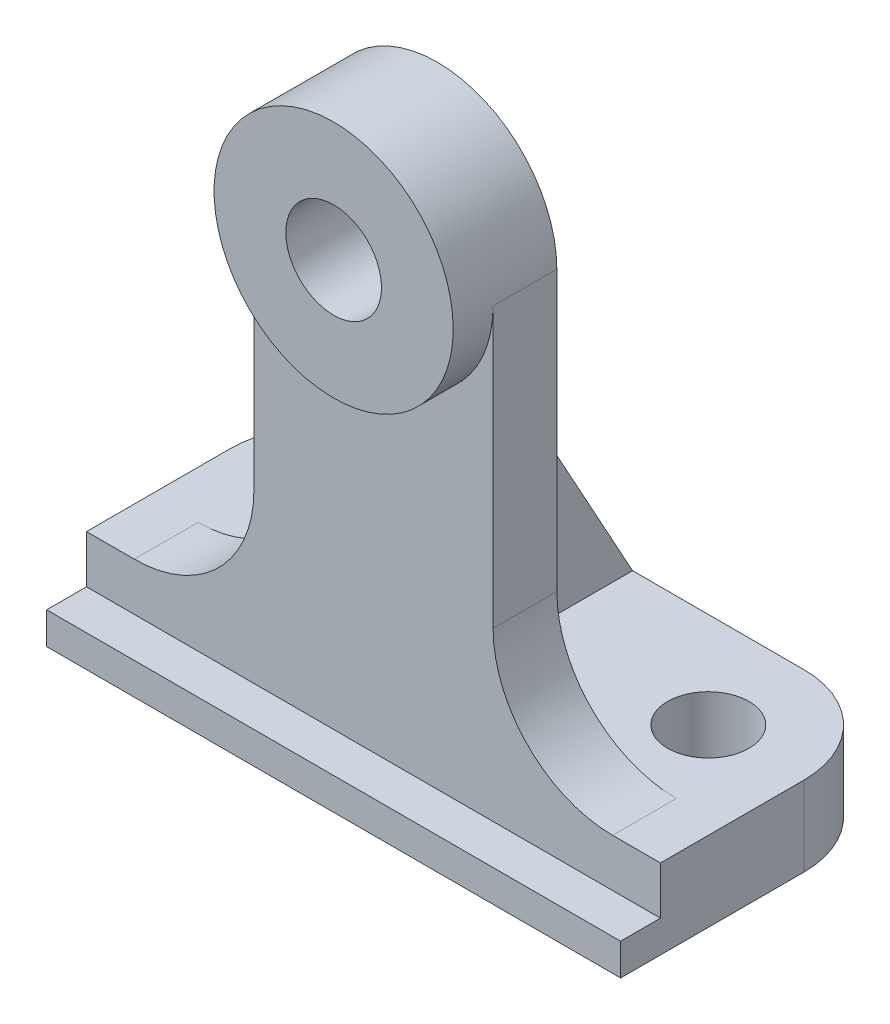
SolidWorks part; units mm, degrees
ref_plane "Front Plane" through (0, 0, 0) normal (0, 0, 1) x (1, 0, 0)
ref_plane "Top Plane" through (0, 0, 0) normal (0, 1, 0) x (1, 0, 0)
ref_plane "Right Plane" through (0, 0, 0) normal (1, 0, 0) x (0, 0, -1)
sketch "Sketch1" plane through (0, 0, 0) normal (0, 0, 1) x (1, 0, 0)
  line L0 (-36, 0) -> (36, 0)
  line L1 (36, 0) -> (36, 10)
  line L2 (36, 10) -> (30, 10)
  line L3 (-36, 10) -> (-36, 0)
  line L6 (15, 60) -> (15, 25)
  line L7 (-15, 60) -> (-15, 25)
  line L8 (-30, 10) -> (-36, 10)
  circle A0 centre (0, 60) radius 15
  circle A1 centre (0, 60) radius 6
  arc A2 (15, 25) -> (30, 10) centre (30, 25) ccw
  arc A3 (-15, 25) -> (-30, 10) centre (-30, 25) cw
  point P4 (0, 0)
  point P17 (-15, 10)
  dimension "D4" = 12
  dimension "D2" = 15
  dimension "D1" = 10
extrude "Boss-Extrude1" add sketch "Sketch1" along normal blind 8 contours L7 A3 L8 L3 L0 L1 L2 A2 L6 A0 region at (0, 19.5776, 0)
extrude "Boss-Extrude2" add sketch "Sketch1<3>" along normal blind 13 contours A0 A1 region at (0, 74.5757, 0)
sketch "Sketch1<3>" plane through (0, 0, 0) normal (0, 0, 1) x (1, 0, 0) same geometry as "Sketch1"
sketch "Sketch2" plane through (0, 0, 0) normal (0, 0, -1) x (-1, 0, 0)
  line L0 (36, 0) -> (-36, 0) construction
  line L1 (-36, 10) -> (36, 10)
  line L2 (-36, 10) -> (-36, 0)
  line L3 (-36, 0) -> (36, 0)
  line L4 (36, 10) -> (36, 0)
extrude "Boss-Extrude3" add sketch "Sketch2" along normal blind 22
sketch "Sketch3" plane through (0, 10, 0) normal (0, 1, 0) x (1, 0, 0)
  line L1 (-24, 22) -> (24, 22)
  line L2 (-36, 10) -> (-36, -8)
  line L3 (-36, -8) -> (36, -8)
  line L4 (36, 10) -> (36, -8)
  line L5 (-36, 22) -> (36, 22)
  line L6 (-36, 22) -> (-36, -8)
  line L7 (-36, -8) -> (36, -8)
  line L8 (36, 22) -> (36, -8)
  arc A0 (24, 22) -> (36, 10) centre (24, 10) cw
  arc A1 (-24, 22) -> (-36, 10) centre (-24, 10) ccw
  circle A2 centre (-24, 10) radius 5.1
  circle A3 centre (24, 10) radius 5.1
  point P10 (-36, 22)
  line M7 (36, -8) -> (36, 22)
  line M8 (36, 22) -> (-36, 22)
  line M9 (-36, 22) -> (-36, -8)
  dimension "D1" = 12
  dimension "D2" = 10.2
  dimension "D3" = 10.2
extrude "Cut-Extrude1" cut sketch "Sketch3" against normal blind 22 contours A0 M8 M7 | A3 | A2 | A1 M8 M9 region at (-33.3196, 10, -19.3196) region at (33.3196, 10, -19.3196) region at (-24, 10, -10) region at (24, 10, -10)
sketch "Sketch4" plane through (0, 0, 8) normal (0, 0, 1) x (1, 0, 0)
  line L1 (-36, 0) -> (36, 0)
  line L2 (-36, 0) -> (-36, 4)
  line L3 (-36, 4) -> (36, 4)
  line L4 (36, 0) -> (36, 4)
  line L5 (36, 0) -> (36, 10) construction
  dimension "D1" = 4
  dimension "D2" = 72
extrude "Boss-Extrude4" add sketch "Sketch4" along normal blind 5
sketch "Sketch5" plane through (0, 0, 0) normal (1, 0, 0) x (0, 0, -1)
  line L0 (0, 10) -> (0, 50)
  line L1 (0, 60) -> (0, 25) construction
  line L2 (0, 50) -> (22, 10)
  line L3 (0, 10) -> (22, 10)
  dimension "D1" = 40
extrude "Boss-Extrude5" add sketch "Sketch5" along normal mid plane 5
